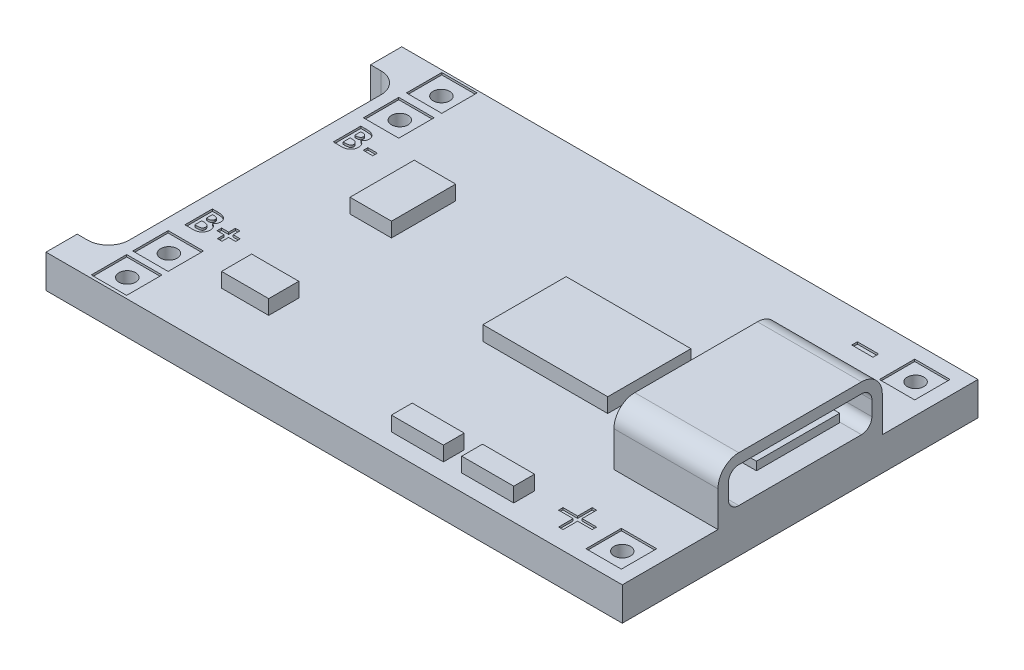
SolidWorks part; units mm, degrees
ref_plane "Front Plane" through (0, 0, 0) normal (0, 0, 1) x (1, 0, 0)
ref_plane "Top Plane" through (0, 0, 0) normal (0, 1, 0) x (1, 0, 0)
ref_plane "Right Plane" through (0, 0, 0) normal (1, 0, 0) x (0, 0, -1)
sketch "Sketch1" plane through (0, 0, 0) normal (0, 1, 0) x (1, 0, 0)
  line L0 (1.5, 17.1) -> (1.5, 0) construction
  line L1 (0, 0) -> (27.7, 0)
  line L2 (0, 0) -> (0, 1.5)
  line L3 (0, 17.1) -> (27.7, 17.1)
  line L4 (27.7, 0) -> (27.7, 17.1)
  line L5 (0, 15.6) -> (0.5, 15.6)
  line L6 (1.5, 14.6) -> (1.5, 2.5)
  line L7 (0.5, 1.5) -> (0, 1.5)
  line L8 (0, 15.6) -> (0, 17.1)
  arc A0 (1.5, 2.5) -> (0.5, 1.5) centre (0.5, 2.5) cw
  arc A1 (0.5, 15.6) -> (1.5, 14.6) centre (0.5, 14.6) cw
  circle A2 centre (2.9074, 16.1) radius 0.4
  circle A3 centre (2.9074, 14.1) radius 0.4
  circle A4 centre (2.9074, 3) radius 0.4
  circle A5 centre (2.9074, 1) radius 0.4
  circle A6 centre (26.2, 15.6) radius 0.4
  circle A7 centre (26.2, 1.5) radius 0.4
  point P13 (1.5, 1.5)
  point P16 (1.5, 15.6)
  point P29 (0, 0)
  dimension "D6" = 1
  dimension "D7" = 1
  dimension "D1" = 27.7
  dimension "D2" = 17.1
  dimension "D3" = 1.5
  dimension "D4" = 1.5
  dimension "D5" = 1.5
  dimension "D8" = 2
  dimension "D9" = 2
  dimension "D10" = 1
  dimension "D11" = 1.5
  dimension "D12" = 1.5
  dimension "D13" = 1.5
  dimension "D14" = 1.5
extrude "Boss-Extrude1" add sketch "Sketch1" along normal blind 1.6
sketch "Sketch2" plane through (0, 1.6, 0) normal (0, 1, 0) x (1, 0, 0)
  line L0 (2.0352, 16.9887) -> (3.7352, 15.2887) construction
  line L1 (2.0352, 16.9887) -> (3.7352, 16.9887)
  line L2 (2.0352, 16.9887) -> (2.0352, 15.2887)
  line L3 (2.0352, 15.2887) -> (3.7352, 15.2887)
  line L4 (3.7352, 16.9887) -> (3.7352, 15.2887)
  line L5 (2.0352, 14.921) -> (3.7352, 13.221) construction
  line L6 (2.0352, 14.921) -> (3.7352, 14.921)
  line L7 (2.0352, 14.921) -> (2.0352, 13.221)
  line L8 (2.0352, 13.221) -> (3.7352, 13.221)
  line L9 (3.7352, 14.921) -> (3.7352, 13.221)
  line L10 (2.039, 3.8314) -> (3.739, 2.1314) construction
  line L11 (2.039, 3.8314) -> (3.739, 3.8314)
  line L12 (2.039, 3.8314) -> (2.039, 2.1314)
  line L13 (2.039, 2.1314) -> (3.739, 2.1314)
  line L14 (3.739, 3.8314) -> (3.739, 2.1314)
  line L15 (2.039, 1.8381) -> (3.739, 0.1381) construction
  line L16 (2.039, 1.8381) -> (3.739, 1.8381)
  line L17 (2.039, 1.8381) -> (2.039, 0.1381)
  line L18 (2.039, 0.1381) -> (3.739, 0.1381)
  line L19 (3.739, 1.8381) -> (3.739, 0.1381)
  line L20 (25.332, 16.4261) -> (27.032, 14.7261) construction
  line L21 (25.332, 16.4261) -> (27.032, 16.4261)
  line L22 (25.332, 16.4261) -> (25.332, 14.7261)
  line L23 (25.332, 14.7261) -> (27.032, 14.7261)
  line L24 (27.032, 16.4261) -> (27.032, 14.7261)
  line L25 (25.3257, 2.33) -> (27.0257, 0.63) construction
  line L26 (25.3257, 2.33) -> (27.0257, 2.33)
  line L27 (25.3257, 2.33) -> (25.3257, 0.63)
  line L28 (25.3257, 0.63) -> (27.0257, 0.63)
  line L29 (27.0257, 2.33) -> (27.0257, 0.63)
  dimension "D1" = 1.7
  dimension "D2" = 1.7
extrude "Cut-Extrude1" cut sketch "Sketch2" against normal blind 0.1
extrude "Cut-Extrude2" cut sketch "Sketch2<2>" along normal blind 0.1 from surface starting at face at (26.2, 0, -15.2)
sketch "Sketch2<2>" plane through (0, 1.6, 0) normal (0, 1, 0) x (1, 0, 0) same geometry as "Sketch2"
sketch "Sketch3" plane through (0, 1.6, 0) normal (0, 1, 0) x (1, 0, 0)
  line L0 (27.7, 0) -> (27.7, 17.1) construction
  line L1 (5.7212, 11.9793) -> (7.7143, 11.9793)
  line L2 (5.7212, 11.9793) -> (5.7212, 8.892)
  line L3 (5.7212, 8.892) -> (7.7143, 8.892)
  line L4 (7.7143, 11.9793) -> (7.7143, 8.892)
  line L5 (5.7212, 4.1632) -> (7.9879, 4.1632)
  line L6 (5.7212, 4.1632) -> (5.7212, 2.7172)
  line L7 (5.7212, 2.7172) -> (7.9879, 2.7172)
  line L8 (7.9879, 4.1632) -> (7.9879, 2.7172)
  line L9 (15.7845, 1.8184) -> (18.2845, 1.8184)
  line L10 (15.7845, 1.8184) -> (15.7845, 0.8184)
  line L11 (15.7845, 0.8184) -> (18.2845, 0.8184)
  line L12 (18.2845, 1.8184) -> (18.2845, 0.8184)
  line L13 (19.1851, 1.7988) -> (21.6851, 1.7988)
  line L14 (19.1851, 1.7988) -> (19.1851, 0.7988)
  line L15 (19.1851, 0.7988) -> (21.6851, 0.7988)
  line L16 (21.6851, 1.7988) -> (21.6851, 0.7988)
  line L17 (14.2201, 10.7816) -> (20.2201, 10.7816)
  line L18 (14.2201, 10.7816) -> (14.2201, 6.7816)
  line L19 (14.2201, 6.7816) -> (20.2201, 6.7816)
  line L20 (20.2201, 10.7816) -> (20.2201, 6.7816)
  line L21 (27.7, 12.5) -> (22.7, 12.5)
  line L22 (27.7, 12.5) -> (27.7, 4.6)
  line L23 (27.7, 4.6) -> (22.7, 4.6)
  line L24 (22.7, 12.5) -> (22.7, 4.6)
  line L25 (0, 0) -> (27.7, 0) construction
  line L27 (27.7, 17.1) -> (0, 17.1) construction
  dimension "D1" = 7.9
  dimension "D2" = 4.6
  dimension "D3" = 4.6
  dimension "D4" = 4
  dimension "D5" = 6
  dimension "D6" = 5
  dimension "D7" = 2.5
  dimension "D8" = 1
extrude "Boss-Extrude2" add sketch "Sketch3" along normal blind 0.7
extrude "Boss-Extrude3" add sketch "Sketch3<2>" along normal blind 2.7 contours L24 L23 L22 L21
sketch "Sketch3<2>" plane through (0, 1.6, 0) normal (0, 1, 0) x (1, 0, 0) same geometry as "Sketch3"
fillet "Fillet1" radius 1 2 edges at (25.2, 4.3, -4.6) (25.2, 4.3, -12.5)
sketch "Sketch4" plane through (27.7, 0, 0) normal (1, 0, 0) x (0, 0, -1)
  line L1 (6.4511, 3.5211) -> (10.4511, 3.5211)
  line L2 (6.4511, 3.5211) -> (6.4511, 3.1211)
  line L3 (6.4511, 3.1211) -> (10.4511, 3.1211)
  line L4 (10.4511, 3.5211) -> (10.4511, 3.1211)
  line L8 (5.1, 3.3) -> (5.1, 1.6)
  line L9 (11.5, 3.8) -> (5.6, 3.8)
  line L10 (5.1, 3.3) -> (5.1, 2.6)
  line L11 (11.5, 3.8) -> (5.6, 3.8)
  line L12 (5.6, 2.1) -> (11.5, 2.1)
  line L13 (12, 1.6) -> (12, 3.3)
  line L14 (12, 2.6) -> (12, 3.3)
  arc A0 (12, 2.6) -> (11.5, 2.1) centre (11.5, 2.6) cw
  arc A1 (5.1, 2.6) -> (5.6, 2.1) centre (5.6, 2.6) ccw
  arc A3 (5.6, 3.8) -> (5.1, 3.3) centre (5.6, 3.3) ccw
  arc A4 (5.6, 3.8) -> (5.1, 3.3) centre (5.6, 3.3) ccw
  arc A6 (12, 3.3) -> (11.5, 3.8) centre (11.5, 3.3) ccw
  arc A7 (12, 3.3) -> (11.5, 3.8) centre (11.5, 3.3) ccw
  dimension "D3" = 0.5
  dimension "D4" = 4
  dimension "D5" = 0.4
  dimension "D1" = 0.5
  dimension "D2" = 0.5
extrude "Cut-Extrude3" cut sketch "Sketch4" against normal blind 4
sketch "Sketch5" plane through (0, 1.6, 0) normal (0, 1, 0) x (1, 0, 0)
  text T0 "+" font "Century Gothic" height in points 9
sketch "Sketch6" plane through (0, 1.6, 0) normal (0, 1, 0) x (1, 0, 0)
  text T0 "-" font "Century Gothic" height in points 10
sketch "Sketch7" plane through (0, 1.6, 0) normal (0, 1, 0) x (1, 0, 0)
  text T0 "<b>B+</b>" font "Century Gothic" height in points 5
  text T1 "<b>B-</b>" font "Century Gothic" height in points 5
extrude "Cut-Extrude4" cut sketch "Sketch7" against normal blind 0.1
extrude "Cut-Extrude5" cut sketch "Sketch6" against normal blind 0.1
extrude "Cut-Extrude6" cut sketch "Sketch5" against normal blind 0.1
